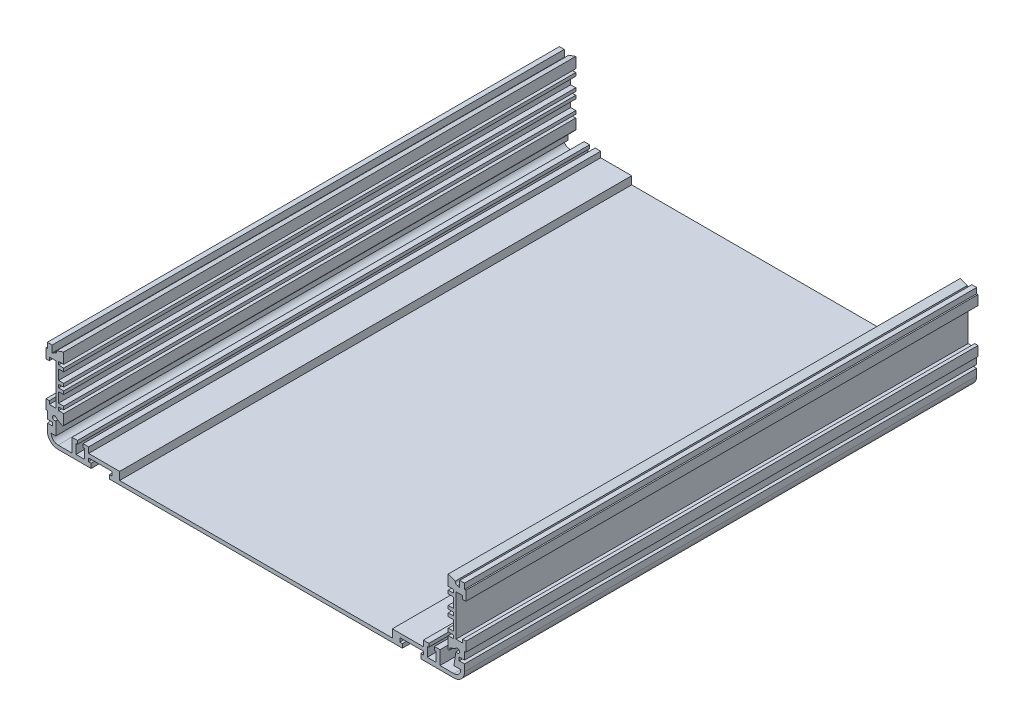
SolidWorks part; units mm, degrees
ref_plane "Front Plane" through (0, 0, 0) normal (0, 0, 1) x (1, 0, 0)
ref_plane "Top Plane" through (0, 0, 0) normal (0, 1, 0) x (1, 0, 0)
ref_plane "Right Plane" through (0, 0, 0) normal (1, 0, 0) x (0, 0, -1)
ref_plane "ExtTop" through (0, 0, 0) normal (0, 1, 0) x (1, 0, 0)
ref_plane "ExtBottom" through (0, -52.07, 0) normal (0, 1, 0) x (1, 0, 0)
ref_plane "ExtRight" through (124.968, 0, 0) normal (1, 0, 0) x (0, 0, -1)
ref_plane "ExtLeft" through (-124.968, 0, 0) normal (1, 0, 0) x (0, 0, -1)
ref_plane "IntBottom" through (0, -41.656, 0) normal (0, 1, 0) x (1, 0, 0)
ref_plane "IntRight" through (117.475, 0, 0) normal (1, 0, 0) x (0, 0, -1)
ref_plane "IntLeft" through (-117.475, 0, 0) normal (1, 0, 0) x (0, 0, -1)
ref_plane "PCBRight" through (117.475, 0, 0) normal (1, 0, 0) x (0, 0, -1)
ref_plane "PCBLeft" through (-117.475, 0, 0) normal (1, 0, 0) x (0, 0, -1)
sketch "Sketch2" plane through (0, 0, 0) normal (0, 0, 1) x (1, 0, 0)
  line L0 (-87.1139, -52.07) -> (87.1139, -52.07)
  line L1 (55, -52.07) -> (-55, -52.07) construction
  line L2 (-87.1139, -52.07) -> (-87.1139, -49.7078)
  line L3 (-87.1139, -49.7078) -> (-85.6138, -49.7078)
  line L4 (-85.6138, -49.7078) -> (-85.6138, -47.3456)
  line L5 (-119.0625, -31.4706) -> (-119.0625, -7.0104)
  line L6 (-85.6138, -47.3456) -> (-99.6138, -47.3456)
  line L7 (-99.6138, -47.3456) -> (-99.6138, -49.3141)
  line L8 (-99.6138, -49.3141) -> (-98.1138, -49.3141)
  line L9 (-98.1138, -49.3141) -> (-98.1138, -52.07)
  line L10 (-98.1138, -52.07) -> (-117.8242, -52.07)
  line L11 (-119.0625, -7.0104) -> (-122.9995, -7.0104)
  line L12 (-124.1742, -45.72) -> (-124.1743, -41.656)
  line L13 (55, -41.656) -> (-55, -41.656) construction
  line L14 (-124.1743, -41.656) -> (-120.9992, -41.656)
  line L15 (-120.9992, -41.656) -> (-120.9992, -39.6875)
  line L16 (-120.9992, -39.6875) -> (-124.1743, -39.6875)
  line L17 (-124.1743, -39.6875) -> (-124.1743, -35.2171)
  line L18 (-124.1743, -35.2171) -> (-124.968, -35.2171)
  line L20 (-124.968, -35.2171) -> (-124.968, -29.5021)
  line L21 (-124.968, -29.5021) -> (-122.9995, -29.5021)
  line L22 (-122.9995, -29.5021) -> (-122.9995, -31.4706)
  line L23 (-122.9995, -31.4706) -> (-119.0625, -31.4706)
  line L24 (-122.9995, -7.0104) -> (-122.9995, -8.9789)
  line L25 (-122.9995, -8.9789) -> (-124.968, -8.9789)
  line L26 (-124.968, -8.9789) -> (-124.968, -3.2639)
  line L27 (-124.968, -3.2639) -> (-124.1743, -3.2639)
  line L28 (-124.1743, -3.2639) -> (-124.1742, 0)
  line L29 (-124.1742, 0) -> (-121.2948, 0)
  line L30 (-114.427, -31.9405) -> (-114.427, -37.9276)
  line L31 (-118.7375, -36.451) -> (-115.3901, -38.4712)
  line L32 (-121.2948, 0) -> (-121.2948, -4.11)
  line L33 (-118.6712, -1.7) -> (-114.427, -0.1905)
  line L34 (-117.475, -28.6385) -> (-117.475, 28.6385) construction
  line L35 (-114.427, -0.1905) -> (-114.427, -6.5405)
  line L36 (-114.427, -6.5405) -> (-117.475, -6.5405)
  line L37 (-117.475, -6.5405) -> (-117.475, -8.4709)
  line L38 (-117.475, -8.4709) -> (-114.427, -8.4709)
  line L39 (-114.427, -8.4709) -> (-114.427, -10.4013)
  line L40 (-114.427, -10.4013) -> (-117.475, -10.4013)
  line L41 (-117.475, -10.4013) -> (-117.475, -16.3449)
  line L42 (-117.475, -16.3449) -> (-114.427, -16.3449)
  line L43 (-114.427, -16.3449) -> (-114.427, -18.2753)
  line L44 (-114.427, -18.2753) -> (-117.475, -18.2753)
  line L45 (-117.475, -18.2753) -> (-117.475, -20.2057)
  line L46 (-117.475, -20.2057) -> (-114.427, -20.2057)
  line L47 (-114.427, -20.2057) -> (-114.427, -22.1361)
  line L48 (-114.427, -22.1361) -> (-117.475, -22.1361)
  line L49 (-117.475, -22.1361) -> (-117.475, -28.0797)
  line L50 (-117.475, -28.0797) -> (-114.427, -28.0797)
  line L51 (-114.427, -28.0797) -> (-114.427, -30.0101)
  line L52 (-114.427, -30.0101) -> (-117.475, -30.0101)
  line L53 (-117.475, -30.0101) -> (-117.475, -31.9405)
  line L54 (-117.475, -31.9405) -> (-114.427, -31.9405)
  line L55 (-121.2948, -4.11) -> (-120.0119, -3.3277)
  line L56 (81.1544, -45.0596) -> (81.1544, -49.784)
  line L57 (-124.968, -55) -> (-124.968, 55) construction
  line L58 (-117.8242, -49.8108) -> (-109.5199, -49.8108)
  line L59 (-119.0494, -37.9425) -> (-119.0494, -45.72)
  line L60 (-109.5199, -49.8108) -> (-109.5199, -41.656)
  line L61 (-109.5199, -41.656) -> (-106.2178, -41.656)
  line L62 (-106.2178, -41.656) -> (-106.2179, -43.6118)
  line L63 (-106.2179, -43.6118) -> (-107.1577, -43.6118)
  line L64 (-107.1577, -43.6118) -> (-107.1577, -49.3141)
  line L65 (-107.1577, -49.3141) -> (-101.976, -49.3141)
  line L66 (-101.976, -49.3141) -> (-101.9761, -43.6118)
  line L67 (-101.9761, -43.6118) -> (-102.9159, -43.6118)
  line L68 (-102.9159, -43.6118) -> (-102.9159, -41.656)
  line L69 (-102.9159, -41.656) -> (-99.6138, -41.656)
  line L70 (-99.6138, -41.656) -> (-99.6138, -45.0596)
  line L71 (-99.6138, -45.0596) -> (-81.1544, -45.0596)
  line L72 (-81.1544, -45.0596) -> (-81.1544, -49.784)
  line L73 (-81.1544, -49.784) -> (81.1544, -49.784)
  line L74 (0, 0) -> (0, -52.07) construction
  line L75 (99.6138, -45.0596) -> (81.1544, -45.0596)
  line L76 (55, 0) -> (-55, 0) construction
  line L77 (99.6138, -41.656) -> (99.6138, -45.0596)
  line L78 (102.9159, -41.656) -> (99.6138, -41.656)
  line L79 (102.9159, -43.6118) -> (102.9159, -41.656)
  line L80 (101.9761, -43.6118) -> (102.9159, -43.6118)
  line L81 (101.976, -49.3141) -> (101.9761, -43.6118)
  line L82 (107.1577, -49.3141) -> (101.976, -49.3141)
  line L83 (107.1577, -43.6118) -> (107.1577, -49.3141)
  line L84 (106.2179, -43.6118) -> (107.1577, -43.6118)
  line L85 (106.2178, -41.656) -> (106.2179, -43.6118)
  line L86 (109.5199, -41.656) -> (106.2178, -41.656)
  line L87 (109.5199, -49.8108) -> (109.5199, -41.656)
  line L88 (117.8242, -45.72) -> (121.9151, -45.72)
  line L89 (117.8242, -49.8108) -> (109.5199, -49.8108)
  line L90 (119.0494, -37.9425) -> (117.8242, -45.72)
  line L91 (121.2948, -4.11) -> (120.0119, -3.3277)
  line L92 (117.475, -31.9405) -> (114.427, -31.9405)
  line L93 (117.475, -30.0101) -> (117.475, -31.9405)
  line L94 (114.427, -30.0101) -> (117.475, -30.0101)
  line L95 (114.427, -28.0797) -> (114.427, -30.0101)
  line L96 (117.475, -28.0797) -> (114.427, -28.0797)
  line L97 (117.475, -22.1361) -> (117.475, -28.0797)
  line L98 (114.427, -22.1361) -> (117.475, -22.1361)
  line L99 (114.427, -20.2057) -> (114.427, -22.1361)
  line L100 (117.475, -20.2057) -> (114.427, -20.2057)
  line L101 (117.475, -18.2753) -> (117.475, -20.2057)
  line L102 (114.427, -18.2753) -> (117.475, -18.2753)
  line L103 (114.427, -16.3449) -> (114.427, -18.2753)
  line L104 (117.475, -16.3449) -> (114.427, -16.3449)
  line L105 (117.475, -10.4013) -> (117.475, -16.3449)
  line L106 (114.427, -10.4013) -> (117.475, -10.4013)
  line L107 (114.427, -8.4709) -> (114.427, -10.4013)
  line L108 (117.475, -8.4709) -> (114.427, -8.4709)
  line L109 (117.475, -6.5405) -> (117.475, -8.4709)
  line L110 (114.427, -6.5405) -> (117.475, -6.5405)
  line L111 (114.427, -0.1905) -> (114.427, -6.5405)
  line L112 (118.6712, -1.7) -> (114.427, -0.1905)
  line L113 (121.2948, 0) -> (121.2948, -4.11)
  line L114 (115.1678, -37.8816) -> (118.7375, -36.451)
  line L115 (114.427, -31.9405) -> (114.427, -39.0525)
  line L116 (124.1742, 0) -> (121.2948, 0)
  line L117 (124.1743, -3.2639) -> (124.1742, 0)
  line L118 (124.968, -3.2639) -> (124.1743, -3.2639)
  line L119 (124.968, -8.9789) -> (124.968, -3.2639)
  line L120 (122.9995, -8.9789) -> (124.968, -8.9789)
  line L121 (122.9995, -7.0104) -> (122.9995, -8.9789)
  line L122 (122.9995, -31.4706) -> (119.0625, -31.4706)
  line L123 (122.9995, -29.5021) -> (122.9995, -31.4706)
  line L124 (124.968, -29.5021) -> (122.9995, -29.5021)
  line L125 (124.968, -35.2171) -> (124.968, -29.5021)
  line L126 (124.1743, -35.2171) -> (124.968, -35.2171)
  line L127 (124.1743, -39.6875) -> (124.1743, -35.2171)
  line L128 (120.9992, -39.6875) -> (124.1743, -39.6875)
  line L129 (120.9992, -41.656) -> (120.9992, -39.6875)
  line L130 (124.1743, -41.656) -> (120.9992, -41.656)
  line L131 (124.1742, -45.72) -> (124.1743, -41.656)
  line L132 (119.0625, -7.0104) -> (122.9995, -7.0104)
  line L133 (98.1138, -52.07) -> (117.8242, -52.07)
  line L134 (98.1138, -49.3141) -> (98.1138, -52.07)
  line L135 (99.6138, -49.3141) -> (98.1138, -49.3141)
  line L136 (99.6138, -47.3456) -> (99.6138, -49.3141)
  line L137 (85.6138, -47.3456) -> (99.6138, -47.3456)
  line L138 (119.0625, -31.4706) -> (119.0625, -7.0104)
  line L139 (85.6138, -49.7078) -> (85.6138, -47.3456)
  line L140 (87.1139, -49.7078) -> (85.6138, -49.7078)
  line L141 (87.1139, -52.07) -> (87.1139, -49.7078)
  line L142 (-119.0494, -45.72) -> (-121.9151, -45.72)
  line L144 (-117.475, -55) -> (-117.475, 55) construction
  arc A0 (-117.8242, -52.07) -> (-124.1742, -45.72) centre (-117.8242, -45.72) cw
  arc A1 (-119.0494, -37.9425) -> (-118.7375, -36.451) centre (-119.888, -36.9887) cw
  arc A2 (-117.8242, -49.8108) -> (-121.9151, -45.72) centre (-117.8242, -45.72) cw
  arc A3 (-115.3901, -38.4712) -> (-114.427, -37.9276) centre (-115.062, -37.9276) ccw
  arc A4 (-118.6712, -1.7) -> (-120.0119, -3.3277) centre (-119.888, -2.0637) cw
  arc A5 (118.6712, -1.7) -> (120.0119, -3.3277) centre (119.888, -2.0637) ccw
  arc A6 (115.1678, -37.8816) -> (114.427, -39.0525) centre (114.7974, -38.467) cw
  arc A7 (117.8242, -49.8108) -> (121.9151, -45.72) centre (117.8242, -45.72) ccw
  arc A8 (119.0494, -37.9425) -> (118.7375, -36.451) centre (119.888, -36.9887) ccw
  arc A9 (117.8242, -52.07) -> (124.1742, -45.72) centre (117.8242, -45.72) ccw
  point P28 (-124.1742, -52.07)
  point P88 (-117.475, -19.2405)
  point P91 (-117.475, -39.8038)
  point P99 (0, -49.784)
  point P110 (0, -49.784)
  point P172 (117.475, -39.8038)
  point P173 (124.1742, -52.07)
  point P174 (-119.0625, -19.2405)
  point P175 (-114.427, -39.0525)
  dimension "D5" = 6.35
  dimension "D8" = 119.888
  dimension "D13" = 0.635
  dimension "D15" = 1.27
  dimension "D1" = 14
  dimension "D2" = 2.3622
  dimension "D3" = 11
  dimension "D4" = 26.0604
  dimension "D6" = 3.175
  dimension "D7" = 5.715
  dimension "D9" = 3.937
  dimension "D10" = 24.4602
  dimension "D11" = 0.7937
  dimension "D12" = 1.5875
  dimension "D14" = 34.925
  dimension "D16" = 6.35
  dimension "D17" = 1.9304
  dimension "D18" = 5.9436
  dimension "D19" = 5.9436
  dimension "D20" = 5.715
  dimension "D21" = 15.0812
  dimension "D24" = 3.302
  dimension "D25" = 3.302
  dimension "D26" = 2.3622
  dimension "D27" = 1.9558
  dimension "D28" = 2.286
  dimension "D30" = 4.4704
extrude "MainBody" add sketch "Sketch2" along normal blind 304.8
ref_plane "BodyFront" through (0, 0, 304.8) normal (0, 0, 1) x (1, 0, 0)
ref_plane "BodyBack" through (0, 0, 0) normal (0, 0, -1) x (-1, 0, 0)
ref_plane "BottomSlot" through (0, -31.9405, 0) normal (0, 1, 0) x (1, 0, 0)
ref_plane "MiddleSlot" through (0, -20.2057, 0) normal (0, 1, 0) x (1, 0, 0)
ref_plane "TopSlot" through (0, -8.4709, 0) normal (0, 1, 0) x (1, 0, 0)
ref_plane "LRCenter" through (0, 0, 0) normal (1, 0, 0) x (0, 0, -1)
ref_plane "FBCenter" through (0, 0, 152.4) normal (0, 0, 1) x (1, 0, 0)
ref_axis "MntTR" through (119.888, -2.0637, 304.8) along (0, 0, -1)
ref_axis "MntBR" through (119.888, -36.9887, 304.8) along (0, 0, -1)
ref_axis "MntBL" through (-119.888, -36.9887, 304.8) along (0, 0, -1)
ref_axis "MntTL" through (-119.888, -2.0637, 304.8) along (0, 0, -1)
equation "\"ExtBodyDepth\"=12"
equation "\"D1@MainBody\" = \"ExtBodyDepth\""
